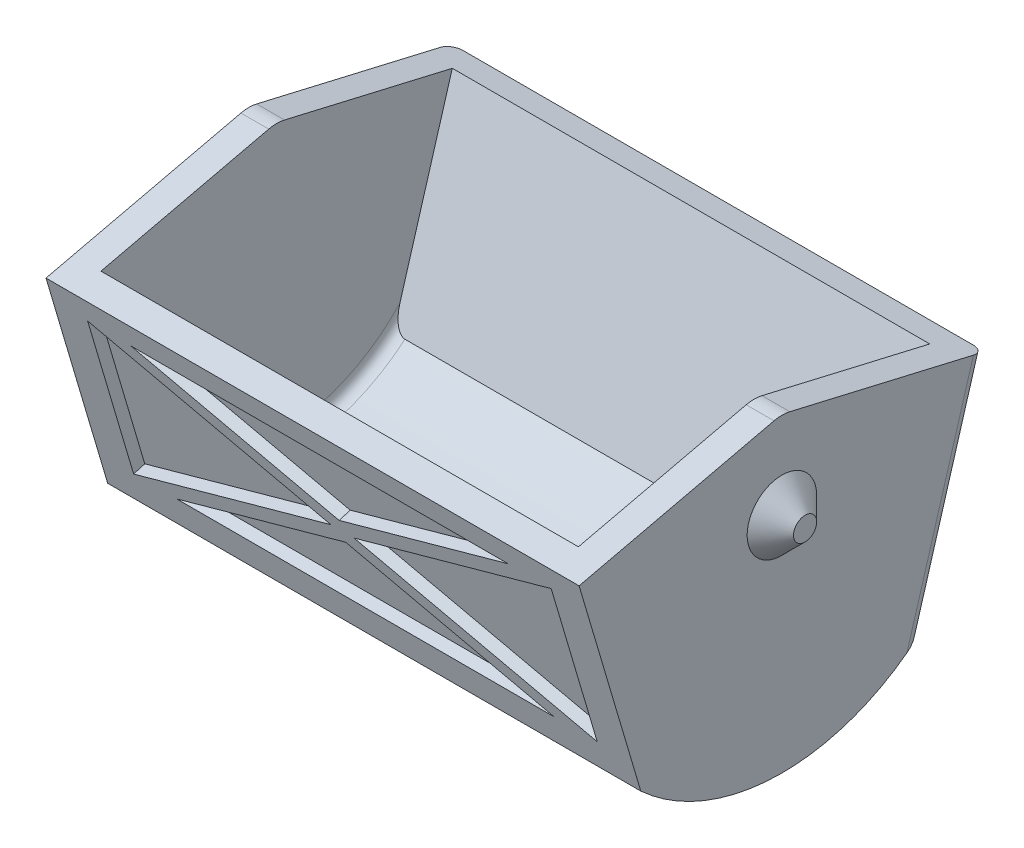
SolidWorks part; units mm, degrees
material "ABS"
ref_plane "Front Plane" through (0, 0, 0) normal (0, 0, 1) x (1, 0, 0)
ref_plane "Top Plane" through (0, 0, 0) normal (0, 1, 0) x (1, 0, 0)
ref_plane "Right Plane" through (0, 0, 0) normal (1, 0, 0) x (0, 0, -1)
sketch "Sketch1" plane through (0, 0, 0) normal (1, 0, 0) x (0, 0, -1)
  line L0 (-12.1763, -9.5264) -> (-17.5, 8.4736)
  line L1 (-17.5, 8.4736) -> (-0.6812, 12.3952)
  line L2 (12.1763, -9.5264) -> (17.5, 8.4736)
  line L3 (17.5, 8.4736) -> (0.6812, 12.3952)
  line L4 (-17.5, 8.4736) -> (17.5, 8.4736) construction
  line L5 (-12.1763, -9.5264) -> (12.1763, -9.5264) construction
  arc A0 (12.1763, -9.5264) -> (-12.1763, -9.5264) centre (0, 3.7302) cw
  arc A1 (-0.6812, 12.3952) -> (0.6812, 12.3952) centre (0, 9.4736) cw
  point P7 (0, -9.5264)
  point P10 (0, 8.4736)
  point P11 (0, 0)
  point P12 (0, 0)
  point P13 (0, 4.5997)
  dimension "D3" = 1
  dimension "D4" = 3
  dimension "D5" = 18
  dimension "D1" = 35
  dimension "D2" = 18
extrude "Boss-Extrude1" add sketch "Sketch1" along normal mid plane 46
shell "Shell1" thickness 2.4 removed face at (0, 10.4344, 9.0906) removed face at (0, 12.4344, 0) removed face at (0, 10.4344, -9.0906)
sketch "Sketch2" plane through (0, 0, 0) normal (1, 0, 0) x (0, 0, -1)
  circle A0 centre (0, 5) radius 3
  dimension "D1" = 6
  dimension "D2" = 5
extrude "Boss-Extrude2" add sketch "Sketch2" along normal blind 2 draft 45 from surface starting at face at (23, 3.0033, 0)
extrude "Boss-Extrude3" add sketch "Sketch2<2>" against normal blind 2 draft 45 from surface starting at face at (-23, 3.0033, 0)
sketch "Sketch2<2>" plane through (0, 0, 0) normal (1, 0, 0) x (0, 0, -1) same geometry as "Sketch2"
fillet "Fillet1" radius 1 4 edges at (-20.6, -11.8698, 0) (20.6, -11.8698, 0) (23, -0.5264, -14.8381) (-23, -0.5264, -14.8381)
ref_plane "Plane1" through (0, -4.0779, 13.7878) normal (0, -0.2836, 0.9589) x (1, 0, 0)
sketch "Sketch3" plane through (0, -99.3096, -14.3782) normal (0, 0.2836, -0.9589) x (1, 0, 0)
  line L0 (-20, -96.3096) -> (-1, -103.3096)
  line L1 (-20, -110.3096) -> (20, -110.3096) construction
  line L2 (-20, -110.3096) -> (-20, -96.3096)
  line L3 (-20, -96.3096) -> (20, -96.3096) construction
  line L4 (20, -110.3096) -> (20, -96.3096)
  line L5 (-20, -110.3096) -> (20, -96.3096) construction
  line L6 (-20, -96.3096) -> (20, -110.3096) construction
  line L7 (-1, -103.3096) -> (-20, -110.3096)
  line L8 (1, -103.3096) -> (20, -110.3096)
  line L9 (1, -103.3096) -> (20, -96.3096)
  line L10 (-16.2857, -96.3096) -> (16.2857, -96.3096)
  line L11 (16.2857, -96.3096) -> (0, -102.3096)
  line L12 (0, -102.3096) -> (-16.2857, -96.3096)
  line L13 (-16.2857, -110.3096) -> (16.2857, -110.3096)
  line L14 (16.2857, -110.3096) -> (0, -104.3096)
  line L15 (0, -104.3096) -> (-16.2857, -110.3096)
  point P0 (0, -103.3096)
  point P13 (-2.5547, -1)
  point P15 (2.5547, -1)
  point P16 (0, -110.3096)
  point P17 (0, -96.3096)
  point P18 (0, -100.3096)
  point P19 (0, 0)
  point P20 (0, -99.3096)
  point P21 (0, -99.3096)
  point P22 (0, 0)
  point P23 (0, 0)
  point P24 (0, 0)
  dimension "D1" = 40
  dimension "D2" = 14
  dimension "D3" = 2
  dimension "D4" = 2
extrude "Cut-Extrude1" cut sketch "Sketch3" along normal blind 1
mirror "Mirror1" about plane through (0, 0, 0) normal (0, 0, 1) of "Cut-Extrude1"
